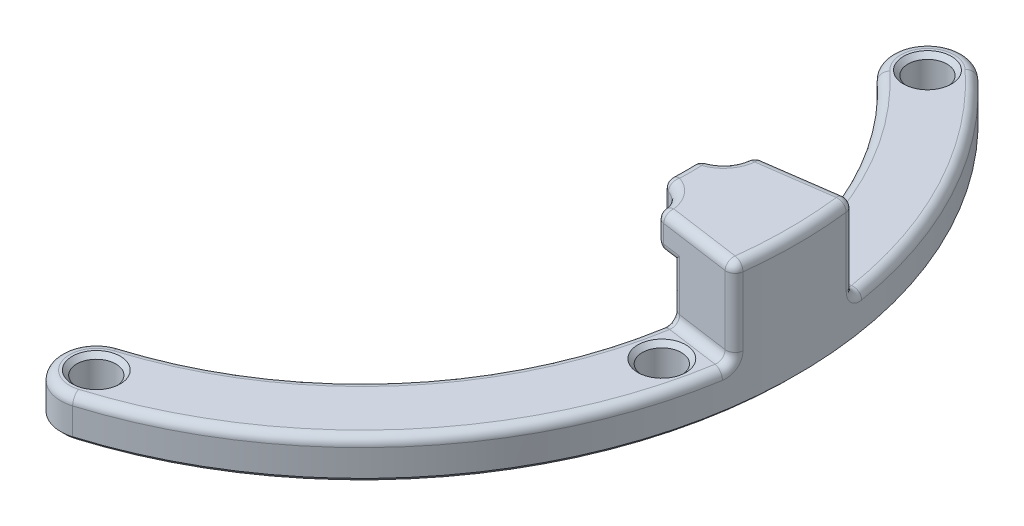
SolidWorks part; units mm, degrees
material "7075-T6, 플레이트 (SS)"
ref_plane "정면" through (0, 0, 0) normal (0, 0, 1) x (1, 0, 0)
ref_plane "윗면" through (0, 0, 0) normal (0, 1, 0) x (1, 0, 0)
ref_plane "우측면" through (0, 0, 0) normal (1, 0, 0) x (0, 0, -1)
sketch "스케치1" plane through (0, 0, 0) normal (0, 1, 0) x (1, 0, 0)
  line L0 (0, -49) -> (0, 0) construction
  line L1 (0, 0) -> (14.3262, -46.8589) construction
  line L2 (0, 0) -> (13.1567, -43.0337) construction
  line L3 (0, 0) -> (43.8467, -10.1228) construction
  line L4 (0, 0) -> (7.6653, -48.3967)
  line L5 (0, 0) -> (28.1052, 40.1385)
  line L6 (30.6899, 32.9109) -> (0, 0) construction
  line L7 (0, 0) -> (48.5231, -6.8195)
  line L8 (0, 0) -> (48.5231, 6.8195)
  line L9 (0, 0) -> (0, 49) construction
  circle A0 centre (0, 0) radius 49
  circle A1 centre (0, 0) radius 45
  circle A2 centre (0, 0) radius 41
  circle A3 centre (13.1567, -43.0337) radius 2.2
  circle A4 centre (43.8467, -10.1228) radius 2.2
  circle A5 centre (30.6899, 32.9109) radius 2.2
  circle A6 centre (0, 0) radius 36
  circle A8 centre (0, 0) radius 43
  circle A9 centre (30.6899, 32.9109) radius 4
  circle A10 centre (13.1567, -43.0337) radius 4
  dimension "D1" = 98
  dimension "D2" = 90
  dimension "D3" = 82
  dimension "D5" = 4.4
  dimension "D10" = 72
  dimension "D11" = 82
  dimension "D12" = 86
  dimension "D4" = 17
  dimension "D7" = 60
  dimension "D8" = 8
  dimension "D9" = 8
  dimension "D13" = 82
  dimension "D6" = 3
extrude "보스-돌출1" add sketch "스케치1" along normal blind 4.5 contours A8 A9 A5 | A1 A9 A8 A5 | A1 A9 A5 | A8 A9 A1 A5 | A9 A2 L8 A8 | A9 A8 L8 A1 | A9 A1 L8 A0 | A4 A8 L8 A2 L7 | A8 A4 A1 L8 | A4 L7 A0 L8 A1 | A10 A8 A4 L7 A2 | A10 A1 A4 A8 | A10 A0 L7 A4 A1 | A8 A10 A3 | A8 A10 A1 A3 | A10 A1 A3 | A1 A10 A8 A3 | A8 A4 A1 L7 region at (41.8716, 0, 0) region at (41.5273, 0, 6.3004) region at (37.1666, 0, -18.0349) region at (12.319, 0, 40.2935) region at (28.7357, 0, -30.8153) region at (43.8647, 0, 0) region at (43.3291, 0, 7.1331) region at (39.2859, 0, -18.3481) region at (10.168, 0, 42.7544) region at (15.4783, 0, 41.1308) region at (32.5965, 0, 28.6774) region at (27.8812, 0, -33.97) region at (31.9424, 0, -30.1829) region at (46.8757, 0, 0) region at (46.4687, 0, 7.0668) region at (41.7844, 0, -20.0026) region at (10.1841, 0, 43.9301) region at (30.4671, 0, -36.8063)
extrude "보스-돌출2" add sketch "스케치1<5>" along normal blind 5.7 from surface contours A4 A8 L8 A2 L7 | A8 A4 A1 L8 | A4 L7 A0 L8 A1 region at (41.8716, 0, 0) region at (43.8647, 0, 0) region at (46.8757, 0, 0) starting at face at (13.1567, 4.5, 45.2337)
sketch "스케치1<5>" plane through (0, 0, 0) normal (0, 1, 0) x (1, 0, 0) same geometry as "스케치1"
extrude "보스-돌출3" add sketch "스케치1<6>" along normal blind 4 from surface contours A6 L7 A2 L8 | A4 A8 L8 A2 L7 | A8 A4 A1 L8 | A4 L7 A0 L8 A1 region at (38.429, 0, 0) region at (41.8716, 0, 0) region at (43.8647, 0, 0) region at (46.8757, 0, 0) starting at face at (44.781, 10.2, 0)
sketch "스케치1<6>" plane through (0, 0, 0) normal (0, 1, 0) x (1, 0, 0) same geometry as "스케치1"
sketch "스케치3" plane through (0, 14.2, 0) normal (0, 1, 0) x (1, 0, 0)
  line L0 (44.3828, -6.4113) -> (48.4966, -7.0056)
  line L1 (48.4966, -7.0056) -> (44.3828, -6.4113)
  line L2 (42.7015, -13.6937) -> (46.6595, -14.9629)
  circle A0 centre (43.8467, -10.1228) radius 3.75
  arc A1 (48.5231, -6.8195) -> (48.5231, 6.8195) centre (0, 0) ccw construction
  arc A2 (14.3262, -46.8589) -> (48.5231, -6.8195) centre (0, 0) ccw construction
  arc A3 (46.6595, -14.9629) -> (48.4966, -7.0056) centre (0, 0) ccw
  dimension "D1" = 7.5
extrude "컷-돌출1" [suppressed] cut sketch "스케치3" against normal blind 9.7
sketch "스케치4" plane through (0, 14.2, 0) normal (0, 1, 0) x (1, 0, 0)
  circle A0 centre (35.6497, 5.0102) radius 3
  circle A1 centre (35.6497, -5.0102) radius 3
  dimension "D1" = 6
extrude "컷-돌출2" cut sketch "스케치4" against normal blind 4
chamfer "모따기1" distance 0.5 angle 45 7 edges at (30.6899, 4.5, -30.7109) (27.7645, 0, -35.6389) (47.7441, 0, 11.0226) (39.9492, 0, 9.223) (9.3315, 0, 44.2032) (43.8467, 4.5, 12.3228) (13.1567, 4.5, 45.2337)
fillet "필렛4" radius 1 25 edges at (31.1766, 4.5, 26.6274) (27.7645, 4.5, -35.6389) (37.2599, 4.5, 31.823) (9.3315, 4.5, 44.2032) (48.5231, 9.35, 6.8195) (43.5718, 14.2, 6.1236) (43.5718, 14.2, -6.1236) (49, 14.2, 0) (48.5231, 9.35, -6.8195) (40.601, 7.35, -5.7061) (40.601, 7.35, 5.7061) (44.5621, 4.5, -6.2628) (44.5621, 4.5, 6.2628) (38.0074, 10.2, 3.1553) (36, 10.2, 0) (38.0074, 10.2, -3.1553) (38.0074, 14.2, 3.1553) (36, 14.2, 0) (38.0074, 14.2, -3.1553) (35.943, 12.2, 2.0246) (35.943, 12.2, -2.0246) (38.6205, 12.2, -5.4278) (38.6205, 12.2, 5.4278) (39.6107, 10.2, 5.5669) (39.6107, 10.2, -5.5669)
